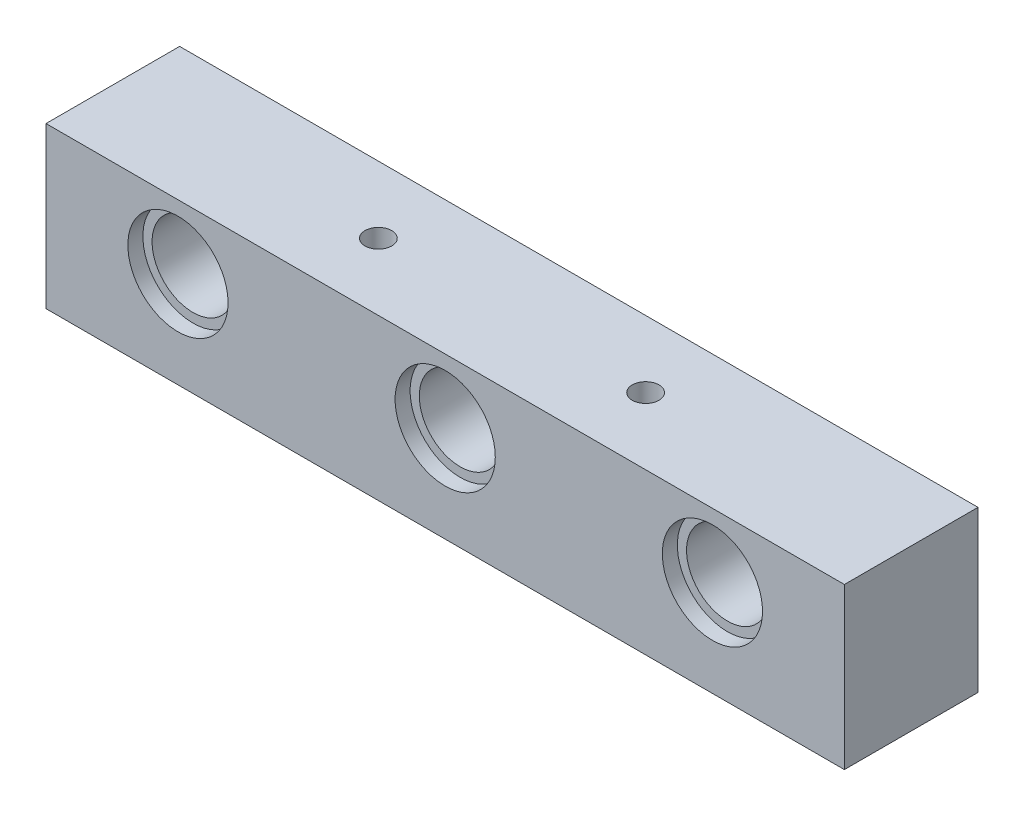
SolidWorks part; units mm, degrees
material "3.1325 (EN-AW 2017A)"
ref_plane "Ebene vorne" through (0, 0, 0) normal (0, 0, 1) x (1, 0, 0)
ref_plane "Ebene oben" through (0, 0, 0) normal (0, 1, 0) x (1, 0, 0)
ref_plane "Ebene rechts" through (0, 0, 0) normal (1, 0, 0) x (0, 0, -1)
sketch "Skizze1" plane through (0, 0, 0) normal (0, 0, 1) x (1, 0, 0)
  line L0 (-23.9, 0) -> (23.9, 0) construction
  line L1 (-23.9, 4.8) -> (23.9, 4.8)
  line L2 (-23.9, 4.8) -> (-23.9, -4.8)
  line L3 (-23.9, -4.8) -> (23.9, -4.8)
  line L4 (23.9, 4.8) -> (23.9, -4.8)
  dimension "D1" = 9.6
  dimension "D2" = 47.8
extrude "Aufsatz-Linear austragen1" add sketch "Skizze1" along normal mid plane 8
sketch "Skizze2" plane through (0, 0, 4) normal (0, 0, 1) x (1, 0, 0)
  line L0 (-16, 0.95) -> (0, 0.95) construction
  line L1 (0, 0.95) -> (16, 0.95) construction
  line L2 (0, 4.8) -> (0, -4.8) construction
  line L3 (23.9, 4.8) -> (-23.9, 4.8) construction
  line L4 (-23.9, -4.8) -> (23.9, -4.8) construction
  circle A0 centre (-16, 0.95) radius 2.45
  circle A1 centre (0, 0.95) radius 2.45
  circle A2 centre (16, 0.95) radius 2.45
  circle A3 centre (-16, 0.95) radius 3
  circle A4 centre (0, 0.95) radius 3
  circle A5 centre (16, 0.95) radius 3
  dimension "D2" = 4.9
  dimension "D4" = 6
  dimension "D1" = 16
  dimension "D3" = 5.75
extrude "Schnitt-Linear austragen1" cut sketch "Skizze2" against normal through all contours A0 | A1 | A2 region at (-16, 0.95, 4) region at (0, 0.95, 4) region at (16, 0.95, 4)
extrude "Schnitt-Linear austragen2" cut sketch "Skizze2<3>" against normal blind 0.9
sketch "Skizze2<3>" plane through (0, 0, 4) normal (0, 0, 1) x (1, 0, 0) same geometry as "Skizze2"
mirror "Spiegeln1" about plane through (0, 0, 0) normal (0, 0, 1) of "Schnitt-Linear austragen2"
hole_wizard "M2 Gewindebohrung1" positions "Skizze4" profile "Skizze3" tap size "M2" standard "DIN" end condition through all
sketch "Skizze4" plane through (0, -4.8, 0) normal (0, -1, 0) x (-1, 0, 0)
  line L0 (8, 0) -> (0, 0) construction
  line L1 (0, 0) -> (-8, 0) construction
  point P0 (-8, 0)
  point P2 (8, 0)
  dimension "D1" = 8
cosmetic thread "Bohrungsgewinde1" parameters "D2"=2
cosmetic thread "Bohrungsgewinde2" parameters "D2"=2
sketch "Skizze3" plane through (8, -4.8, 0) normal (1, 0, 0) x (0, 0, -1)
  line L0 (0, 0) -> (0, 9.6)
  line L1 (0, 9.6) -> (0.8, 9.6)
  line L2 (0.8, 9.6) -> (0.8, 0)
  line L5 (0.8, 0) -> (0, 0)
  line L11 (0, -6.35) -> (0, 107.95) construction
  dimension "Bohrerdurchmesser" = 1.6
  dimension "Bohrungstiefe" = 9.6
sketch "Skizze5" plane through (0, -4.8, 0) normal (0, -1, 0) x (1, 0, 0)
  line L0 (-20, 0) -> (-12, 0) construction
  line L1 (-12, 0) -> (-4, 0) construction
  line L2 (-4, 0) -> (4, 0) construction
  line L3 (4, 0) -> (12, 0) construction
  line L4 (12, 0) -> (20, 0) construction
  circle A0 centre (-20, 0) radius 2.45
  circle A1 centre (-4, 0) radius 2.45
  circle A2 centre (-12, 0) radius 2.45
  circle A3 centre (4, 0) radius 2.45
  circle A4 centre (12, 0) radius 2.45
  circle A5 centre (20, 0) radius 2.45
  dimension "D1" = 4.9
  dimension "D2" = 8
extrude "Schnitt-Linear austragen3" cut sketch "Skizze5" against normal blind 2
